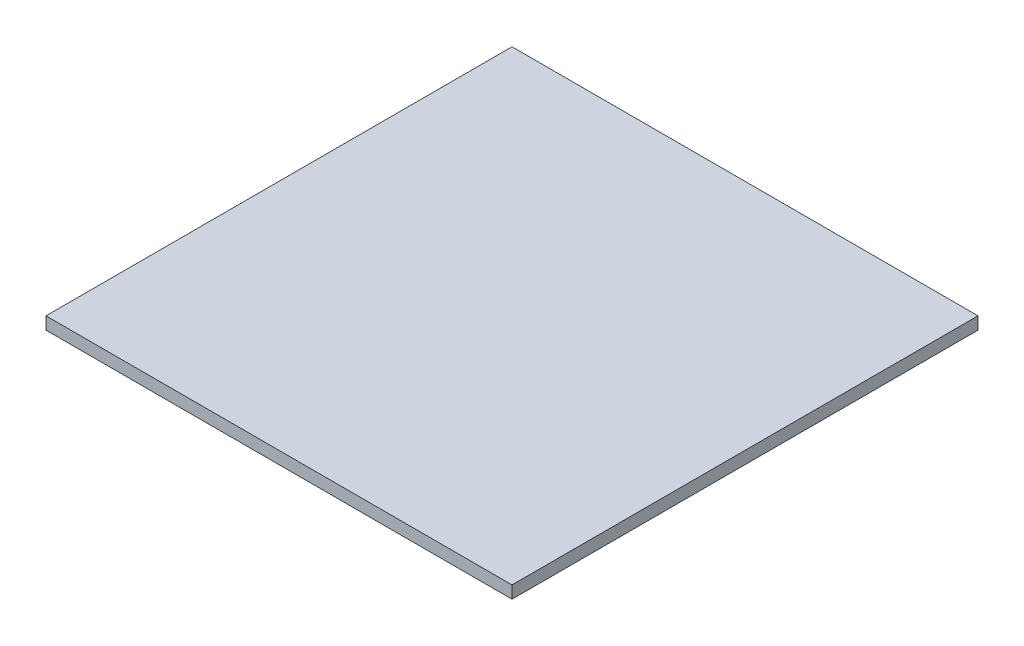
SolidWorks part; units mm, degrees
ref_plane "Plan de face" through (0, 0, 0) normal (0, 0, 1) x (1, 0, 0)
ref_plane "Plan de dessus" through (0, 0, 0) normal (0, 1, 0) x (1, 0, 0)
ref_plane "Plan de droite" through (0, 0, 0) normal (1, 0, 0) x (0, 0, -1)
sketch "Esquisse1" plane through (0, 0, 0) normal (0, 1, 0) x (1, 0, 0)
  line L1 (-150, -150) -> (150, -150)
  line L2 (-150, -150) -> (-150, 150)
  line L3 (-150, 150) -> (150, 150)
  line L4 (150, -150) -> (150, 150)
  line L5 (-150, -150) -> (150, 150) construction
  line L6 (-150, 150) -> (150, -150) construction
  point P0 (0, 0)
  dimension "D1" = 300
extrude "Boss.-Extru.1" add sketch "Esquisse1" along normal blind 8
